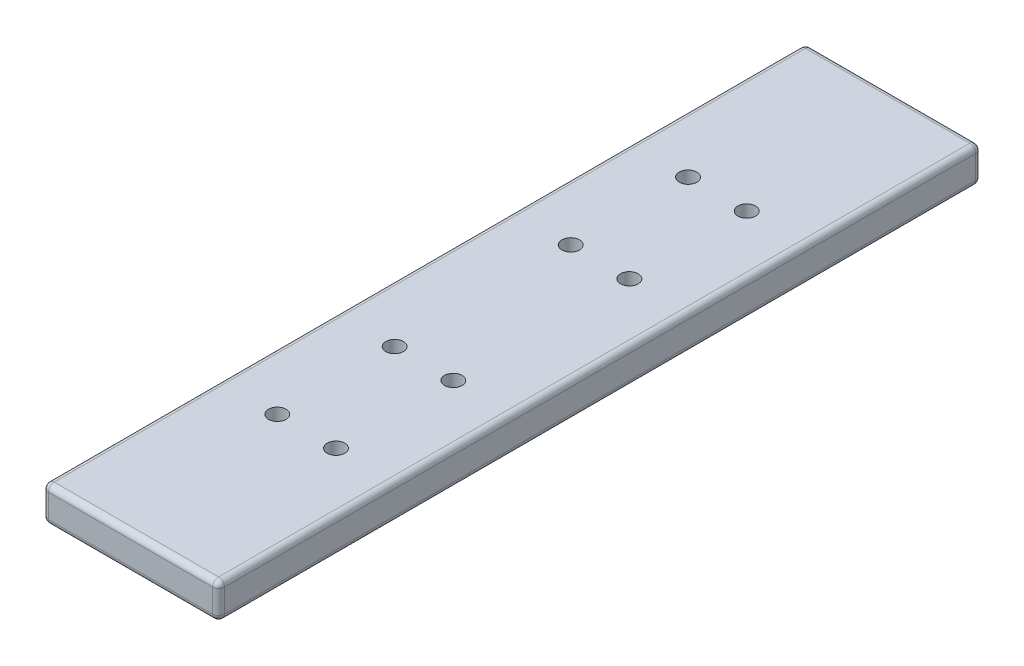
SolidWorks part; units mm, degrees
ref_plane "Front Plane" through (0, 0, 0) normal (0, 0, 1) x (1, 0, 0)
ref_plane "Top Plane" through (0, 0, 0) normal (0, 1, 0) x (1, 0, 0)
ref_plane "Right Plane" through (0, 0, 0) normal (1, 0, 0) x (0, 0, -1)
sketch "Sketch2" plane through (0, 0, 0) normal (0, 0, 1) x (1, 0, 0)
  line L1 (-15, -3) -> (15, -3)
  line L2 (-15, -3) -> (-15, 3)
  line L3 (-15, 3) -> (15, 3)
  line L4 (15, -3) -> (15, 3)
  line L5 (0, 3) -> (0, -3) construction
  line L6 (-15, 0) -> (15, 0) construction
  point P0 (0, 0)
  dimension "D1" = 6
  dimension "D2" = 30
extrude "Boss-Extrude1" add sketch "Sketch2" along normal blind 130
sketch "Sketch3" plane through (0, 3, 0) normal (0, 1, 0) x (1, 0, 0)
  line L0 (-15, -65) -> (15, -65) construction
  line L1 (-15, -130) -> (-15, 0) construction
  line L2 (15, -130) -> (15, 0) construction
  line L3 (-5, -130) -> (-5, -100) construction
  line L4 (15, -130) -> (-15, -130) construction
  line L5 (-5, -100) -> (-15, -100) construction
  circle A0 centre (-5, -100) radius 1.5
  circle A1 centre (5, -100) radius 1.5
  circle A2 centre (5, -80) radius 1.5
  circle A3 centre (-5, -80) radius 1.5
  circle A4 centre (-5, -50) radius 1.5
  circle A5 centre (5, -50) radius 1.5
  circle A6 centre (5, -30) radius 1.5
  circle A7 centre (-5, -30) radius 1.5
  dimension "D3" = 3
  dimension "D4" = 2
  dimension "D5" = 2
  dimension "D1" = 30
  dimension "D2" = 10
extrude "Cut-Extrude3" cut sketch "Sketch3" against normal through all
fillet "Fillet1" radius 1 12 edges at (15, 0, 0) (-15, 0, 0) (-15, 0, 130) (15, 0, 130) (-15, -3, 65) (0, -3, 130) (15, -3, 65) (0, -3, 0) (15, 3, 65) (0, 3, 130) (-15, 3, 65) (0, 3, 0)
